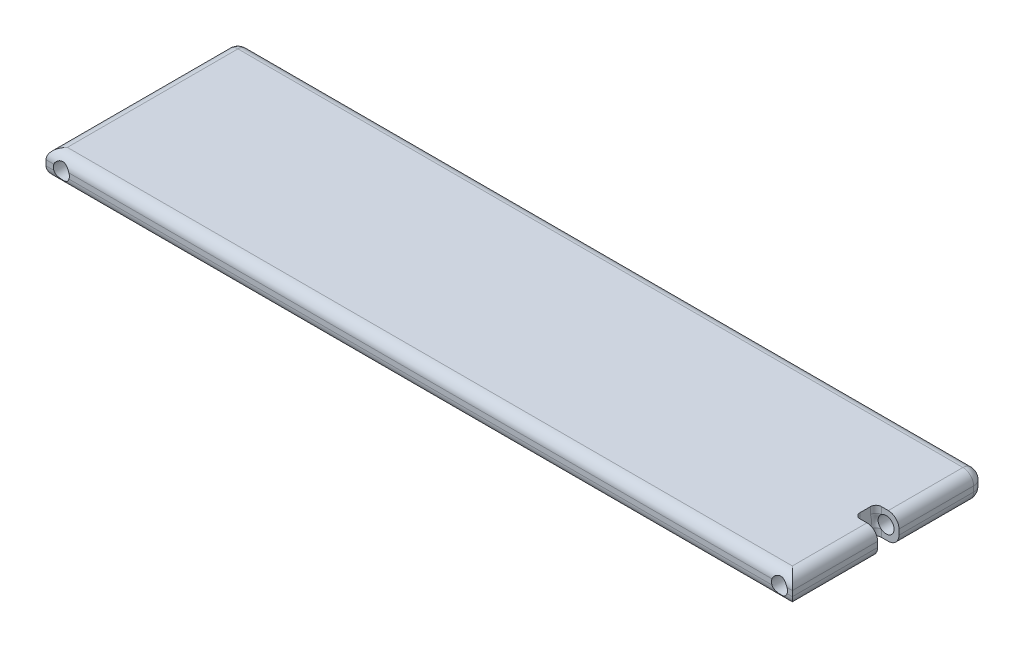
SolidWorks part; units mm, degrees
ref_plane "Front Plane" through (0, 0, 0) normal (0, 0, 1) x (1, 0, 0)
ref_plane "Top Plane" through (0, 0, 0) normal (0, 1, 0) x (1, 0, 0)
ref_plane "Right Plane" through (0, 0, 0) normal (1, 0, 0) x (0, 0, -1)
sketch "Sketch1" plane through (0, 0, 0) normal (0, 1, 0) x (1, 0, 0)
  line L0 (-34.893, 0) -> (35.107, 0) construction
  line L1 (-34.893, 9) -> (-34.893, -9)
  line L2 (35.107, 9) -> (35.107, -9)
  line L3 (-34.893, 9) -> (35.107, 9)
  line L4 (-34.893, -9) -> (35.107, -9)
  point P5 (-34.893, 0)
  dimension "D1" = 70
  dimension "D2" = 18
  dimension "D3" = 18
extrude "Boss-Extrude1" add sketch "Sketch1" along normal mid plane 2.5
fillet "Fillet1" radius 1 10 edges at (35.107, 1.25, 0) (0.107, 1.25, 9) (-34.893, 1.25, 0) (35.107, 0, -9) (0.107, 1.25, -9) (-34.893, 0, -9) (0.107, -1.25, -9) (-34.893, -1.25, 0) (35.107, -1.25, 0) (0.107, -1.25, 9)
sketch "Sketch2" plane through (0, 0, 0) normal (0, 0, 1) x (1, 0, 0)
  circle A0 centre (-33.4499, 0) radius 0.75
  dimension "D1" = 1.5
extrude "Cut-Extrude1" cut sketch "Sketch2" against normal through all both and the other way through all
sketch "Sketch3" plane through (0, 0, 0) normal (0, 0, 1) x (1, 0, 0)
  circle A0 centre (33.9011, 0) radius 0.75
  dimension "D1" = 1.5
extrude "Cut-Extrude2" cut sketch "Sketch3" against normal through all both and the other way through all
sketch "Sketch4" plane through (0, 0, 0) normal (0, 1, 0) x (1, 0, 0)
  line L1 (35.107, -1) -> (32.9511, -1)
  line L2 (35.107, -1) -> (35.107, 1)
  line L3 (35.107, 1) -> (32.9511, 1)
  line L4 (32.9511, -1) -> (32.9511, 1)
  point P4 (35.107, 0)
  dimension "D1" = 0.2
  dimension "D2" = 2
extrude "Cut-Extrude3" cut sketch "Sketch4" against normal through all both and the other way through all
fillet "Fillet2" radius 0.5 2 edges at (32.9511, 0, 1) (32.9511, 0, -1)
